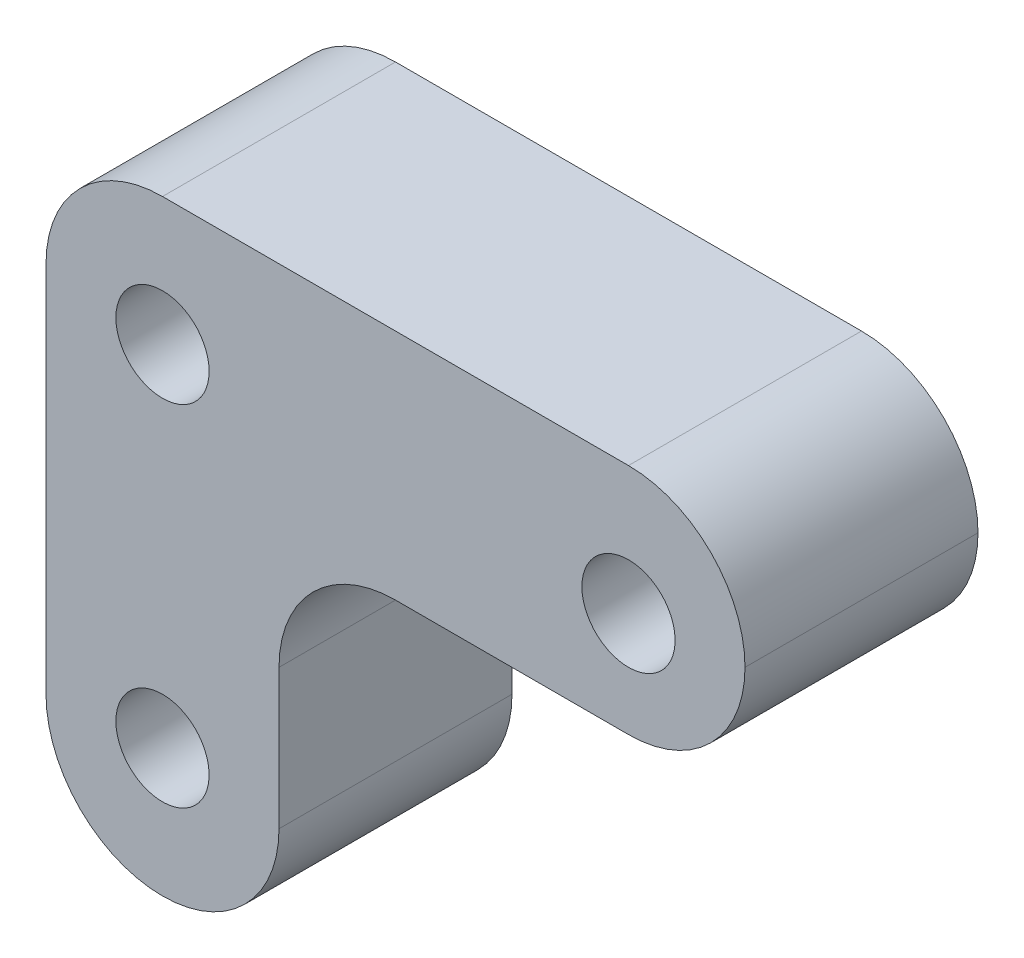
SolidWorks part; units mm, degrees
ref_plane "Front" through (0, 0, 0) normal (0, 0, 1) x (1, 0, 0)
ref_plane "Top" through (0, 0, 0) normal (0, 1, 0) x (1, 0, 0)
ref_plane "Right" through (0, 0, 0) normal (1, 0, 0) x (0, 0, -1)
sketch "Esquisse1" plane through (0, 0, 0) normal (0, 0, 1) x (1, 0, 0)
  line L1 (0, 0) -> (30, 0)
  line L2 (0, 0) -> (0, 26)
  line L3 (0, 26) -> (30, 26)
  line L4 (30, 0) -> (30, 26)
  dimension "D1" = 30
  dimension "D2" = 26
extrude "Boss.-Extru.1" add sketch "Esquisse1" along normal blind 10
sketch "Esquisse2" plane through (0, 0, 10) normal (0, 0, 1) x (1, 0, 0)
  line L0 (15, 0) -> (15, 26) construction
  line L1 (0, 0) -> (30, 0) construction
  line L2 (30, 26) -> (0, 26) construction
  line L3 (15, 13) -> (0, 13) construction
  line L4 (0, 26) -> (0, 0) construction
  circle A0 centre (5, 20.5) radius 2
  circle A1 centre (25, 20.5) radius 2
  circle A2 centre (25, 5.5) radius 2
  circle A3 centre (5, 5.5) radius 2
  dimension "D1" = 15
  dimension "D2" = 20
  dimension "D3" = 4
extrude "Enlèv. mat.-Extru.1" cut sketch "Esquisse2" against normal through all both and the other way through all
sketch "Esquisse3" plane through (0, 0, 10) normal (0, 0, 1) x (1, 0, 0)
  line L0 (30, 26) -> (0, 26) construction
  line L1 (30, 0) -> (10, 0)
  line L2 (30, 0) -> (30, 16)
  line L3 (30, 16) -> (10, 16)
  line L4 (10, 0) -> (10, 16)
  line L5 (0, 26) -> (0, 0) construction
  dimension "D1" = 10
  dimension "D2" = 10
extrude "Enlèv. mat.-Extru.2" cut sketch "Esquisse3" against normal through all both and the other way through all
fillet "Congé1" radius 5 6 edges at (10, 16, 5) (0, 26, 5) (0, 0, 5) (10, 0, 5) (30, 26, 5) (30, 16, 5)
